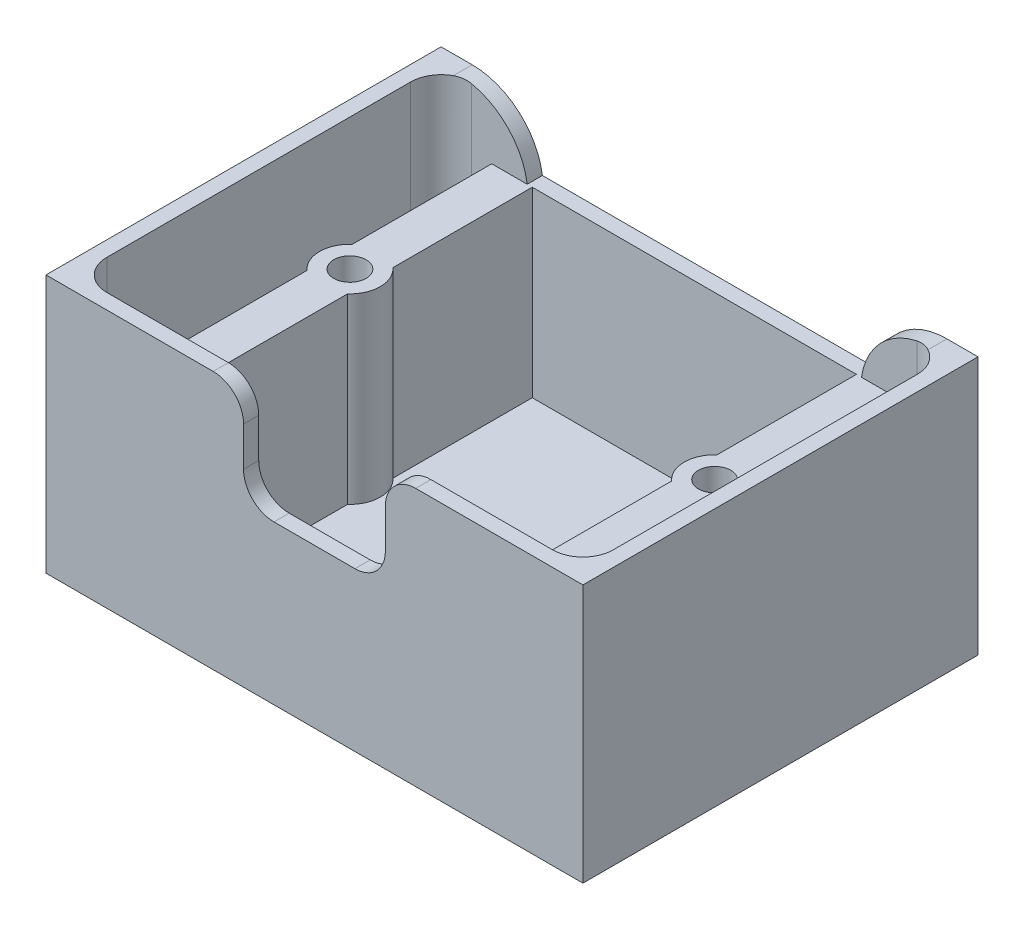
SolidWorks part; units mm, degrees
ref_plane "Front Plane" through (0, 0, 0) normal (0, 0, 1) x (1, 0, 0)
ref_plane "Top Plane" through (0, 0, 0) normal (0, 1, 0) x (1, 0, 0)
ref_plane "Right Plane" through (0, 0, 0) normal (1, 0, 0) x (0, 0, -1)
sketch "Sketch1" plane through (0, 0, 0) normal (0, 1, 0) x (1, 0, 0)
  line L1 (0, 0) -> (50, 0)
  line L2 (0, 0) -> (0, -36)
  line L3 (0, -36) -> (50, -36)
  line L4 (50, 0) -> (50, -36)
  dimension "D1" = 50
  dimension "D2" = 36
extrude "Boss-Extrude1" add sketch "Sketch1" along normal blind 24
shell "Shell1" thickness 1.5 removed face at (25, 24, 18) outward yes
sketch "Sketch2" plane through (0, 0, 0) normal (0, 1, 0) x (1, 0, 0)
  line L0 (50, 0) -> (0, 0) construction
  line L1 (5, 0) -> (9, 0)
  line L2 (5, 0) -> (5, -36)
  line L3 (5, -36) -> (9, -36)
  line L4 (9, 0) -> (9, -36)
  line L5 (0, -36) -> (50, -36) construction
  line L6 (25, 0) -> (25, -71.172) construction
  line L7 (45, -36) -> (41, -36)
  line L8 (41, 0) -> (41, -36)
  line L9 (45, 0) -> (41, 0)
  line L10 (45, 0) -> (45, -36)
  dimension "D1" = 4
  dimension "D2" = 16
extrude "Boss-Extrude2" add sketch "Sketch2" along normal blind 18
sketch "Sketch3" plane through (0, 0, 0) normal (0, 1, 0) x (1, 0, 0)
  line L0 (-7.5821, -25) -> (66.7821, -25) construction
sketch "Sketch4" plane through (0, 18, 0) normal (0, 1, 0) x (1, 0, 0)
  line L0 (25, -36) -> (25, -57.4435) construction
  line L2 (0, -36) -> (50, -36) construction
  circle A0 centre (7, -16) radius 3
  circle A2 centre (43, -16) radius 3
  dimension "D1" = 6
  dimension "D2" = 18
  dimension "D3" = 20
sketch "Sketch6" plane through (0, 0, 37.5) normal (0, 0, 1) x (1, 0, 0)
  line L0 (25, 24) -> (25, -9.6606) construction
  line L1 (18, 14.1347) -> (32, 14.1347)
  line L2 (18, 14.1347) -> (18, 28.1347)
  line L3 (18, 28.1347) -> (32, 28.1347)
  line L4 (32, 14.1347) -> (32, 28.1347)
  line L5 (-1.5, 24) -> (51.5, 24) construction
  dimension "D1" = 14
  dimension "D2" = 7
  dimension "D3" = 14
extrude "Cut-Extrude2" cut sketch "Sketch6" against normal blind 10
fillet "Fillet1" radius 3 8 edges at (50, 12, 36) (0, 12, 36) (50, 12, 0) (0, 12, 0) (18, 24, 36.75) (18, 14.1347, 36.75) (32, 14.1347, 36.75) (32, 24, 36.75)
extrude "Boss-Extrude3" add sketch "Sketch4" against normal up to surface (18 mm away) up to face at (25, 0, 18)
sketch "Sketch7" plane through (0, 18, 0) normal (0, 1, 0) x (1, 0, 0)
  line L0 (25, -36) -> (25, -57.6999) construction
  line L1 (29, -36) -> (21, -36) construction
  line L2 (5, -36) -> (9, -36) construction
  circle A0 centre (7, -16) radius 1.6
  circle A1 centre (43, -16) radius 1.6
  dimension "D1" = 18
  dimension "D3" = 3.2
  dimension "D2" = 20
extrude "Cut-Extrude3" cut sketch "Sketch7" against normal blind 12
sketch "Sketch8" plane through (0, 0, -1.5) normal (0, 0, -1) x (-1, 0, 0)
  line L0 (-51.5, 24) -> (1.5, 24) construction
  line L1 (-41.5, 18) -> (-8.5, 18)
  line L2 (-41.5, 18) -> (-41.5, 26)
  line L3 (-41.5, 26) -> (-8.5, 26)
  line L4 (-8.5, 18) -> (-8.5, 26)
  line L5 (1.5, 24) -> (1.5, -1.5) construction
  dimension "D1" = 2
  dimension "D2" = 8
  dimension "D3" = 33
  dimension "D4" = 10
extrude "Cut-Extrude4" cut sketch "Sketch8" against normal blind 5
fillet "Fillet3" radius 7 2 edges at (41.5, 24, -0.75) (8.5, 24, -0.75)
